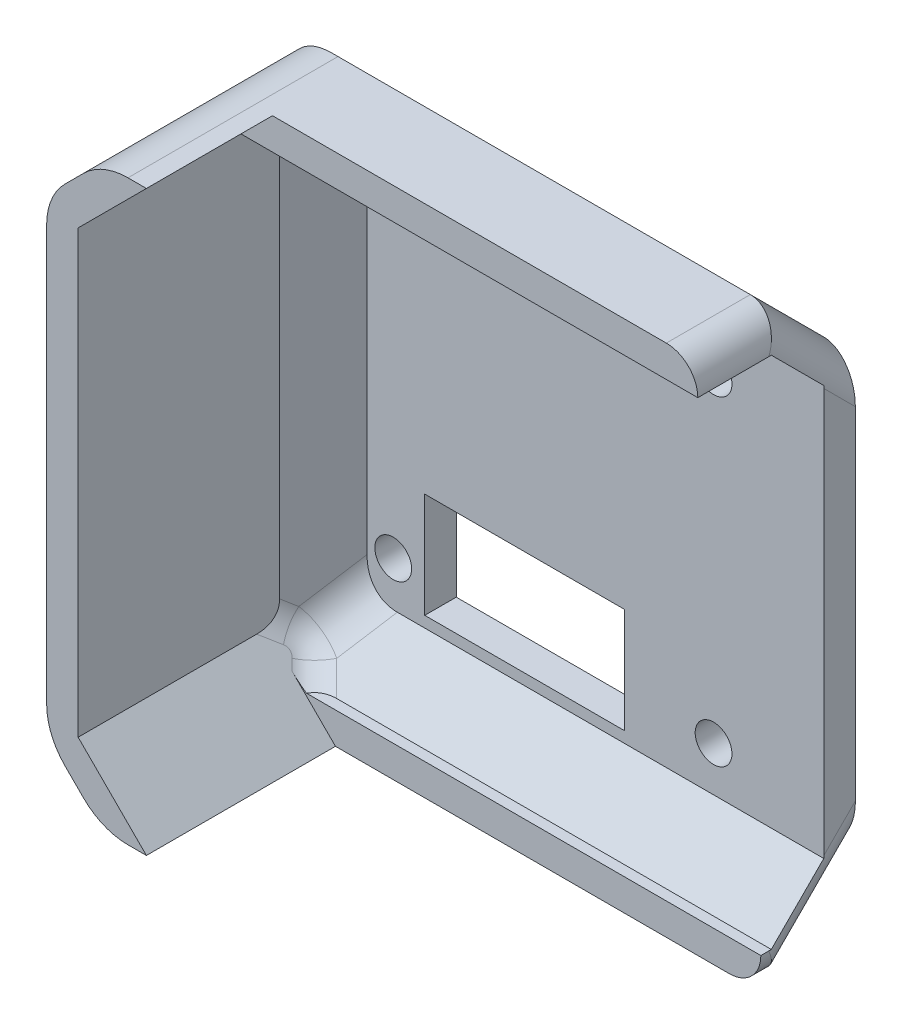
SolidWorks part; units mm, degrees
ref_plane "Plan de face" through (0, 0, 0) normal (0, 0, 1) x (1, 0, 0)
ref_plane "Plan de dessus" through (0, 0, 0) normal (0, 1, 0) x (1, 0, 0)
ref_plane "Plan de droite" through (0, 0, 0) normal (1, 0, 0) x (0, 0, -1)
sketch "Esquisse1" plane through (0, 0, 0) normal (0, 0, 1) x (1, 0, 0)
  line L0 (-24.25, 0) -> (25.75, 0) construction
  line L1 (-24.25, 27.5) -> (25.75, 27.5)
  line L2 (-24.25, 27.5) -> (-24.25, -27.5)
  line L3 (-24.25, -27.5) -> (25.75, -27.5)
  line L4 (25.75, 27.5) -> (25.75, -27.5)
  line L5 (-15.25, 15.25) -> (15.25, 15.25) construction
  line L6 (-15.25, 15.25) -> (-15.25, -15.25) construction
  line L7 (-15.25, -15.25) -> (15.25, -15.25) construction
  line L8 (15.25, 15.25) -> (15.25, -15.25) construction
  line L9 (-15.25, 15.25) -> (15.25, -15.25) construction
  circle A1 centre (15.25, 15.25) radius 1.75
  circle A2 centre (-15.25, -15.25) radius 1.75
  circle A3 centre (15.25, -15.25) radius 1.75
  dimension "D6" = 3.5
  dimension "D7" = 3.5
  dimension "D8" = 3.5
  dimension "D1" = 50
  dimension "D2" = 55
  dimension "D3" = 30.5
  dimension "D4" = 30.5
  dimension "D9" = 9
extrude "Boss.-Extru.1" add sketch "Esquisse1" along normal blind 3
sketch "Esquisse3" plane through (0, 0, 3) normal (0, 0, 1) x (1, 0, 0)
  line L0 (25.75, -27.5) -> (25.75, -24.5)
  line L1 (25.75, -27.5) -> (25.75, 27.5) construction
  line L2 (-17.75, -24.5) -> (85.7448, -24.5) construction
  line L3 (25.75, -27.5) -> (-18.9926, -27.5)
  line L4 (-24.25, -27.5) -> (25.75, -27.5) construction
  line L5 (-18.9926, -27.5) -> (-24.25, -22.2426)
  line L6 (-24.25, 27.5) -> (-24.25, -27.5) construction
  line L7 (-24.25, -22.2426) -> (-24.25, 22.2426)
  line L8 (-24.25, 22.2426) -> (-18.9926, 27.5)
  line L9 (25.75, 27.5) -> (-24.25, 27.5) construction
  line L10 (-18.9926, 27.5) -> (25.75, 27.5)
  line L11 (25.75, 27.5) -> (25.75, 24.5)
  line L12 (25.75, 24.5) -> (-17.75, 24.5)
  line L14 (-17.75, 24.5) -> (-21.25, 21)
  line L15 (-21.25, 21) -> (-21.25, -21)
  line L16 (-21.25, -21) -> (-17.75, -24.5)
  line L17 (-21.25, -21) -> (-14.75, -27.5) construction
  line L18 (-17.75, -24.5) -> (25.75, -24.5)
  line L19 (85.7448, 24.5) -> (-17.75, 24.5) construction
  dimension "D1" = 3
  dimension "D2" = 3
extrude "Boss.-Extru.2" add sketch "Esquisse3" along normal blind 24
sketch "Esquisse6" plane through (0, 0, 3) normal (0, 0, 1) x (1, 0, 0)
  line L0 (-24.25, -27.5) -> (-24.25, -22.2426)
  line L1 (-24.25, -22.2426) -> (-18.9926, -27.5)
  line L2 (-18.9926, -27.5) -> (-24.25, -27.5)
  line L3 (-24.25, 27.5) -> (-18.9926, 27.5)
  line L4 (-18.9926, 27.5) -> (-24.25, 22.2426)
  line L5 (-24.25, 22.2426) -> (-24.25, 27.5)
  line L6 (-18.9926, 27.5) -> (-24.25, 27.5) construction
extrude "Enlèv. mat.-Extru.5" cut sketch "Esquisse6" against normal through all
chamfer "Chanfrein2" distance 5 angle 45 3 edges at (-21.25, 0, 3)
chamfer "Chanfrein1" distance 7 angle 45 5 edges at (3.3787, -27.5, 0) (-21.6213, -24.8713, 0) (-24.25, 0, 0) (-21.6213, 24.8713, 0) (3.3787, 27.5, 0)
chamfer "Chanfrein3" distance 3.5 angle 54 1 edges at (-21.25, 0, 3)
sketch "Esquisse7" plane through (0, 0, 0) normal (0, 0, -1) x (-1, 0, 0)
  line L0 (-15.25, -15.25) -> (15.25, -15.25) construction
  line L1 (-6.75, -8.45) -> (12.25, -8.45)
  line L2 (-6.75, -8.45) -> (-6.75, -18.45)
  line L3 (-6.75, -18.45) -> (12.25, -18.45)
  line L4 (12.25, -8.45) -> (12.25, -18.45)
  dimension "D1" = 3.2
  dimension "D2" = 3
  dimension "D3" = 19
  dimension "D4" = 10
extrude "Enlèv. mat.-Extru.6" cut sketch "Esquisse7" against normal through all
sketch "Esquisse8" plane through (0, 0, 27) normal (0, 0, 1) x (1, 0, 0)
  line L0 (-17.75, 24.5) -> (-14.75, 27.5)
  line L1 (25.75, 27.5) -> (-18.9926, 27.5) construction
  line L2 (-14.75, 27.5) -> (25.75, 27.5)
  line L3 (25.75, 27.5) -> (25.75, 24.5)
  line L4 (25.75, 24.5) -> (-17.75, 24.5)
  line L5 (-17.75, -24.5) -> (-14.75, -27.5)
  line L6 (-18.9926, -27.5) -> (25.75, -27.5) construction
  line L7 (-14.75, -27.5) -> (25.75, -27.5)
  line L8 (25.75, -27.5) -> (25.75, -24.5)
  line L9 (25.75, -24.5) -> (-17.75, -24.5)
  dimension "D1" = 45
extrude "Enlèv. mat.-Extru.7" cut sketch "Esquisse8" against normal blind 12
sketch "Esquisse10" plane through (0, 0, 15) normal (0, 0, 1) x (1, 0, 0)
  line L0 (-17.75, -24.5) -> (-14.75, -27.5)
  line L1 (-14.75, -27.5) -> (25.75, -27.5)
  line L2 (25.75, -27.5) -> (25.75, -24.5)
  line L3 (25.75, -24.5) -> (-17.75, -24.5)
extrude "Enlèv. mat.-Extru.9" cut sketch "Esquisse10" against normal blind 6
chamfer "Chanfrein5" distance 5 angle 54 1 edges at (-24.25, 0, 0)
fillet "Congé7" radius 6 4 edges
fillet "Congé8" radius 10 2 edges at (-20.6687, 22.4526, 1.9526) (-20.6687, -22.4526, 1.9526)
fillet "Congé9" radius 4 2 edges at (-18.802, 20.948, 4.448) (-18.802, -20.948, 4.448)
fillet "Congé10" radius 3 4 edges at (25.75, 24, 3.5) (25.75, -24, 3.5) (25.75, -27.5, 8) (25.75, 27.5, 11)
fillet "Congé11" radius 3 6 edges at (-17.9653, -24.2847, 7.7847) (-21.2476, -21.0024, 7.814) (-21.2476, 21.0024, 7.814) (-17.9653, 24.2847, 7.7847) (-19.7774, -22.4726, 6.8703) (-19.7774, 22.4726, 6.8703)
